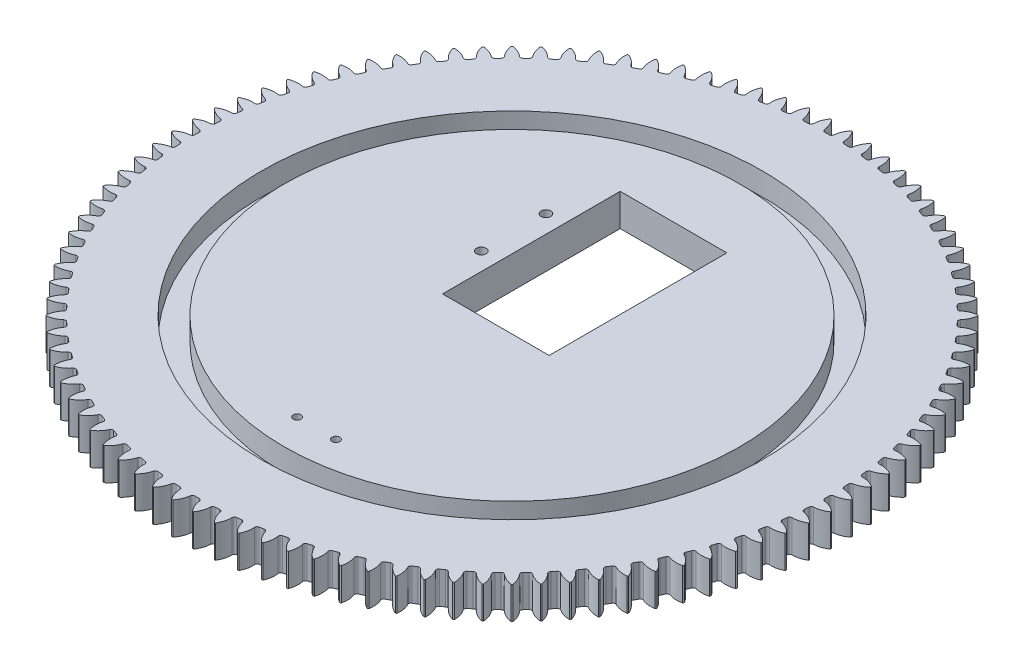
SolidWorks part; units mm, degrees
ref_plane "Front Plane" through (0, 0, 0) normal (0, 0, 1) x (1, 0, 0)
ref_plane "Top Plane" through (0, 0, 0) normal (0, 1, 0) x (1, 0, 0)
ref_plane "Right Plane" through (0, 0, 0) normal (1, 0, 0) x (0, 0, -1)
sketch "Sketch1" plane through (0, 0, 0) normal (0, 1, 0) x (1, 0, 0)
  circle A1 centre (0, 0) radius 102
  dimension "D2" = 204
extrude "Boss-Extrude1" add sketch "Sketch1" along normal blind 10
sketch "Sketch2" plane through (0, 10, 0) normal (0, 1, 0) x (1, 0, 0)
  line L0 (0, 0) -> (0, 102) construction
  line L1 (-1.3895, 97.4901) -> (0, 0) construction
  line L2 (0, 94.8463) -> (-2.5918, 101.9671) construction
  circle A0 centre (0, 0) radius 102 construction
  arc A1 (1.3895, 97.4901) -> (-1.3895, 97.4901) centre (0, 0) ccw
  arc A2 (1.8707, 99.9825) -> (-1.8707, 99.9825) centre (0, 0) ccw construction
  arc A3 (3.0148, 101.9554) -> (-3.0148, 101.9554) centre (0, 0) ccw
  arc A4 (-3.0148, 101.9554) -> (-1.3895, 97.4901) centre (-8.6195, 97.387) cw
  arc A5 (3.0148, 101.9554) -> (1.3895, 97.4901) centre (8.6195, 97.387) ccw
  point P16 (-1.8249, 99.8601)
  dimension "D1" = 204
  dimension "D2" = 200
  dimension "D3" = 4.5
  dimension "D4" = 20
  dimension "D5" = 3.7416
extrude "Cut-Extrude1" cut sketch "Sketch2" against normal through all
fillet "Fillet1" radius 0.76 2 edges at (1.3895, 5, -97.4901) (-1.3895, 5, -97.4901)
pattern_circular "CirPattern2" count 100 over 360 about axis through (0, 0, 0) along (0, 1, 0) of "Cut-Extrude1", "Fillet1"
sketch "Sketch3" plane through (0, 10, 0) normal (0, 1, 0) x (1, 0, 0)
  circle A0 centre (0, 0) radius 73 construction
  circle A1 centre (0, 0) radius 77.5
  circle A2 centre (0, 0) radius 70.5
  dimension "D1" = 146
  dimension "D2" = 7
  dimension "D3" = 4.5
extrude "Cut-Extrude2" cut sketch "Sketch3" against normal blind 7
sketch "Sketch4" plane through (0, 0, 0) normal (0, -1, 0) x (1, 0, 0)
  circle A0 centre (0, 0) radius 100 construction
  dimension "D1" = 200
sketch "Sketch6" plane through (0, 0, 0) normal (0, -1, 0) x (1, 0, 0)
  line L1 (-16.5, -50) -> (16.5, -50)
  line L2 (-16.5, -50) -> (-16.5, 5)
  line L3 (-16.5, 5) -> (16.5, 5)
  line L4 (16.5, -50) -> (16.5, 5)
  point P4 (0, 5)
  dimension "D1" = 33
  dimension "D2" = 55
  dimension "D3" = 5
extrude "Cut-Extrude3" cut sketch "Sketch6" against normal through all
ref_plane "Plane1" through (21.5, 0, 0) normal (1, 0, 0) x (0, 0, -1)
sketch "Sketch7" plane through (21.5, 0, 0) normal (1, 0, 0) x (0, 0, -1)
  line L1 (1.5, 0) -> (43.5, 0)
  line L2 (1.5, 0) -> (1.5, -47)
  line L3 (1.5, -47) -> (43.5, -47)
  line L4 (43.5, 0) -> (43.5, -47)
  line L5 (50, 10) -> (-5, 10) construction
  circle A0 centre (22.5, -26) radius 12
  circle A1 centre (7, -10.5) radius 1.65
  circle A2 centre (38, -10.5) radius 1.65
  circle A3 centre (38, -41.5) radius 1.65
  circle A4 centre (7, -41.5) radius 1.65
  point P5 (22.5, 0)
  point P18 (22.5, -47)
  point P21 (22.5, 10)
  dimension "D4" = 24
  dimension "D9" = 3.3
  dimension "D1" = 42
  dimension "D2" = 21
  dimension "D3" = 47
  dimension "D5" = 5.5
  dimension "D6" = 10.5
  dimension "D7" = 5.5
  dimension "D8" = 5.5
extrude "Boss-Extrude2" add sketch "Sketch7" along normal blind 5
sketch "Sketch9" plane through (0, 0, 0) normal (0, -1, 0) x (1, 0, 0)
  line L1 (26.5, -1.5) -> (68.5, -1.5)
  line L2 (26.5, -1.5) -> (26.5, -43.5)
  line L3 (26.5, -43.5) -> (68.5, -43.5)
  line L4 (68.5, -1.5) -> (68.5, -43.5)
  dimension "D1" = 42
extrude "Boss-Extrude3" add sketch "Sketch9" along normal blind 5
sketch "Sketch10" plane through (0, 0, 0) normal (0, -1, 0) x (1, 0, 0)
  line L0 (-6, 60.5) -> (6, 60.5) construction
  line L1 (68.5, -1.5) -> (21.5, -1.5) construction
  circle A0 centre (-6, 60.5) radius 1.2
  circle A1 centre (6, 60.5) radius 1.2
  point P2 (0, 60.5)
  dimension "D2" = 2.4
  dimension "D1" = 62
  dimension "D3" = 12
extrude "Cut-Extrude4" cut sketch "Sketch10" against normal through all
sketch "Sketch11" plane through (0, 0, 0) normal (0, -1, 0) x (1, 0, 0)
  line L0 (-16.5, 5) -> (-16.5, -50) construction
  line L1 (-16.5, -22.5) -> (16.5, -22.5) construction
  line L2 (16.5, -50) -> (16.5, 5) construction
  circle A0 centre (-22, -12.5) radius 1.5
  circle A1 centre (-22, -32.5) radius 1.5
  point P4 (-16.5, -22.5)
  dimension "D2" = 3
  dimension "D1" = 5.5
  dimension "D3" = 10
extrude "Cut-Extrude5" cut sketch "Sketch11" against normal through all
equation "\"Module\"= 2"
equation "\"No. of Teeth\"= 100"
equation "\"Bore Diameter\"=2"
equation "\"Pressure Angle\"= 20deg"
equation "\"Outer Diameter\"= ( \"No. of Teeth\" + 2 ) * \"Module\""
equation "\"Pitch Diameter\"= \"No. of Teeth\" * \"Module\""
equation "\"Backlash\"= 0.3 * \"Module\""
equation "\"Arc Length\"= ( \"Module\" * pi ) / 2 + \"Backlash\""
equation "\"Fillet Radius\"= .38 * \"Module\""
equation "\"Tooth Depth\"= IIF ( \"Module\" <= 1.25 , 2.4 * \"Module\" , 2.25 * \"Module\" )"
equation "\"D2@Sketch1\"=\"Outer Diameter\""
equation "\"D2@Sketch2\"=\"Pitch Diameter\""
equation "\"D1@Sketch2\"=\"Outer Diameter\""
equation "\"D3@Sketch2\"=\"Tooth Depth\""
equation "\"D4@Sketch2\"=\"Pressure Angle\""
equation "\"D5@Sketch2\"=\"Arc Length\""
equation "\"D1@Fillet1\"=\"Fillet Radius\""
equation "\"D1@CirPattern2\"=\"No. of Teeth\""
equation "\"D1@Sketch4\"=\"Pitch Diameter\""
